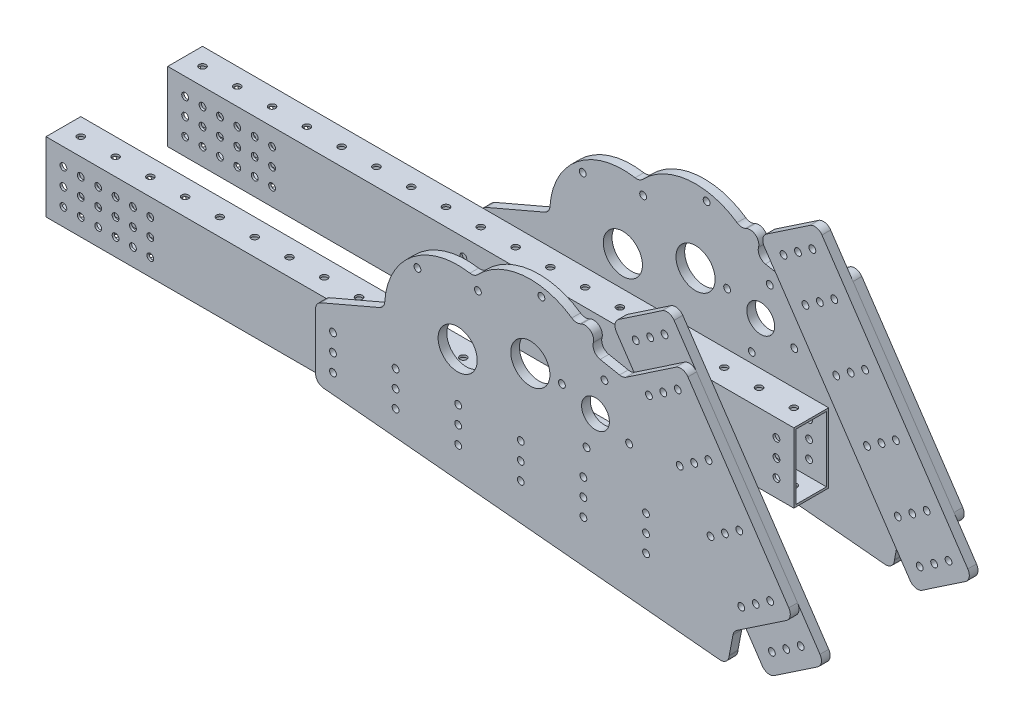
SolidWorks part; units mm, degrees
other "Markup1"
sketch "Sketch2"
sketch "Sketch9" plane through (0, 0, 0) normal (0, 0, 1) x (1, 0, 0)
material "6061-T6 (SS)"
ref_plane "Front Plane" through (0, 0, 0) normal (0, 0, 1) x (1, 0, 0)
ref_plane "Top Plane" through (0, 0, 0) normal (0, 1, 0) x (1, 0, 0)
ref_plane "Right Plane" through (0, 0, 0) normal (1, 0, 0) x (0, 0, -1)
sketch "Grid" plane through (0, 0, 0) normal (0, 0, 1) x (1, 0, 0)
  line L0 (-23.2766, 0) -> (153.3593, 0) construction
  line L1 (0, 0) -> (0, 151.4205) construction
  line L6 (-1009.65, 1168.4) -> (-1009.65, 0) construction
  line L15 (-361.95, 520.7) -> (-803.275, 520.7)
  line L16 (-361.95, 520.7) -> (-361.95, 0)
  line L17 (-361.95, 0) -> (-803.275, 0)
  line L18 (-803.275, 520.7) -> (-803.275, 0)
  line L19 (-803.275, 0) -> (-1244.6, 0)
  line L20 (-803.275, 0) -> (-803.275, 825.5)
  line L21 (-803.275, 825.5) -> (-1244.6, 825.5)
  line L22 (-1244.6, 0) -> (-1244.6, 825.5)
  line L23 (-1030.732, 0) -> (-988.568, 0)
  line L24 (-1030.732, 0) -> (-1030.732, 1168.4)
  line L25 (-1030.732, 1168.4) -> (-988.568, 1168.4)
  line L26 (-988.568, 0) -> (-988.568, 1168.4)
  line L27 (-598.932, 0) -> (-556.768, 0)
  line L28 (-598.932, 0) -> (-598.932, 863.6)
  line L29 (-598.932, 863.6) -> (-556.768, 863.6)
  line L30 (-556.768, 0) -> (-556.768, 863.6)
  line L31 (-577.85, 863.6) -> (-577.85, 0) construction
  line L32 (-361.95, 520.7) -> (-361.95, 596.9) construction
  line L33 (-803.275, 825.5) -> (-803.275, 901.7) construction
  line L34 (-370.0766, 0) -> (-263.7141, 304.8)
  line L35 (-263.7141, 304.8) -> (-157.3516, 0)
  line L36 (-157.3516, 0) -> (-370.0766, 0)
  circle A0 centre (-100.3958, 159.9664) radius 120.65
  dimension "D3" = 241.3
  dimension "D2" = 76.2
  dimension "D4" = 304.8
  dimension "D5" = 212.725
  dimension "D7" = 42.164
  dimension "D8" = 520.7
  dimension "D9" = 304.8
  dimension "D10" = 1168.4
  dimension "D11" = 863.6
  dimension "D12" = 361.95
  dimension "D13" = 577.85
  dimension "D14" = 803.275
  dimension "D15" = 1009.65
sketch "ChassisXY" plane through (0, 0, 0) normal (0, 0, 1) x (1, 0, 0)
  line L0 (755.65, 93.726) -> (95.25, 93.726)
  line L1 (755.65, 93.726) -> (755.65, 42.926)
  line L2 (755.65, 42.926) -> (95.25, 42.926)
  line L3 (95.25, 93.726) -> (95.25, 42.926)
  line L15 (736.7108, 119.126) -> (675.4349, 119.126)
  line L16 (787.4, 42.926) -> (768.35, 42.926)
  line L19 (63.5, 169.926) -> (82.55, 169.926)
  line L20 (736.7108, 119.126) -> (694.5957, 90.719) construction
  line L21 (736.7108, 119.126) -> (717.55, 147.533) construction
  line L22 (694.5957, 90.719) -> (675.4349, 119.126) construction
  line L23 (717.55, 147.533) -> (675.4349, 119.126) construction
  line L27 (63.5, 169.926) -> (63.5, 42.926)
  line L31 (88.9, 42.926) -> (88.9, 1979.9925) construction
  line L32 (62.806, 1979.9925) -> (762, 1979.9925) construction
  line L33 (63.5, 42.926) -> (82.55, 42.926)
  line L36 (88.9, 1320.8) -> (762, 1320.8) construction
  line L37 (88.9, 988.6997) -> (131.0151, 1017.1067) construction
  line L45 (63.5, 42.926) -> (31.75, 42.926)
  line L46 (717.55, 147.533) -> (675.4349, 119.126) construction
  line L47 (717.55, 147.533) -> (-518.4596, 1979.9925) construction
  line L48 (675.4349, 119.126) -> (-560.5747, 1951.5855) construction
  line L49 (-518.4596, 1979.9925) -> (-560.5747, 1951.5855) construction
  line L50 (63.5, 42.926) -> (63.5, 169.926)
  line L51 (0, 74.676) -> (0, 138.176)
  line L52 (31.75, 169.926) -> (63.5, 169.926)
  line L54 (425.45, 93.726) -> (425.45, 42.926) construction
  line L55 (762, 42.926) -> (762, 1979.9925) construction
  line L56 (819.15, 169.926) -> (787.4, 169.926)
  line L57 (850.9, 74.676) -> (850.9, 138.176)
  line L58 (787.4, 42.926) -> (787.4, 169.926)
  line L59 (787.4, 42.926) -> (819.15, 42.926)
  line L60 (82.55, 169.926) -> (82.55, 42.926)
  line L61 (768.35, 169.926) -> (768.35, 42.926)
  line L62 (787.4, 169.926) -> (768.35, 169.926)
  line L63 (787.4, 169.926) -> (787.4, 42.926)
  line L64 (0, 0) -> (0, 200151.4205) construction
  line L65 (-200023.2766, 0) -> (200153.3593, 0) construction
  line L66 (95.25, 152.4) -> (755.65, 152.4) construction
  arc A5 (31.75, 169.926) -> (0, 138.176) centre (31.75, 138.176) ccw
  arc A6 (0, 74.676) -> (31.75, 42.926) centre (31.75, 74.676) ccw
  circle A7 centre (31.75, 74.676) radius 31.75 construction
  circle A8 centre (31.75, 138.176) radius 31.75 construction
  circle A9 centre (819.15, 138.176) radius 31.75 construction
  circle A10 centre (819.15, 74.676) radius 31.75 construction
  arc A11 (850.9, 74.676) -> (819.15, 42.926) centre (819.15, 74.676) cw
  arc A12 (819.15, 169.926) -> (850.9, 138.176) centre (819.15, 138.176) cw
  dimension "D3" = 63.5
  dimension "D1" = 50.8
  dimension "D2" = 56
  dimension "D4" = 38.1
  dimension "D5" = 50.8
  dimension "D6" = 12.7
  dimension "D7" = 19.05
  dimension "D8" = 42.926
  dimension "D9" = 109.474
  dimension "D10" = 25.4
  dimension "D12" = 660.4
  dimension "D13" = 6.35
ref_plane "Plane1" through (561.5696, 378.7835, 0) normal (0.829, 0.5592, 0) x (-0.5592, 0.829, 0)
sketch "carriage geo" plane through (0, 0, 0) normal (0, 0, 1) x (1, 0, 0)
  line L1 (116.0373, 195.326) -> (624.0373, 195.326)
  line L2 (116.0373, 195.326) -> (116.0373, 246.126)
  line L3 (116.0373, 246.126) -> (624.0373, 246.126)
  line L4 (624.0373, 195.326) -> (624.0373, 246.126)
  line L6 (624.0373, 195.326) -> (700.6322, 195.326) construction
  line L17 (717.55, 147.533) -> (-518.4596, 1979.9925) construction
  line L24 (624.0373, 246.126) -> (666.3671, 246.126) construction
  line L33 (666.3671, 246.126) -> (700.6322, 195.326) construction
  line L35 (675.4349, 119.126) -> (-560.5747, 1951.5855) construction
  line L64 (755.65, 93.726) -> (95.25, 93.726) construction
  circle A0 centre (154.1373, 220.726) radius 14.2875
  circle A58 centre (256.8816, 507.741) radius 25.4
  point P4 (353.8882, 537.9448)
  line B0 (120.4355, 364.2548) -> (144.4436, 355.656) construction
  line B1 (345.3934, 565.2279) -> (248.3868, 535.0242)
  line B2 (339.9907, 375.4447) -> (343.9447, 374.0285) construction
  line B3 (348.2442, 386.0326) -> (300.3235, 403.196) construction
  line B4 (308.577, 413.7839) -> (348.5895, 399.4529)
  line B5 (107.1432, 327.1426) -> (206.8255, 291.4401)
  line B6 (112.3162, 360.4178) -> (103.3062, 335.2619)
  line B7 (352.5436, 398.0367) -> (348.5895, 399.4529) construction
  line B8 (366.599, 439.1494) -> (341.413, 442.4393) construction
  line B9 (353.8882, 537.9448) -> (341.413, 442.4393) construction
  line B10 (343.9447, 374.0285) -> (352.5436, 398.0367)
  line B11 (348.5895, 399.4529) -> (308.577, 413.7839)
  line B12 (304.6229, 415.2001) -> (296.0241, 391.1919)
  line B13 (299.9781, 389.7757) -> (339.9907, 375.4447)
  line B14 (140.4752, 344.576) -> (141.8914, 348.5301) construction
  line B15 (129.3385, 325.9381) -> (133.2925, 324.5219) construction
  line B16 (110.7006, 337.0748) -> (109.2844, 333.1207) construction
  line B17 (121.8372, 355.7127) -> (117.8832, 357.1289) construction
  line B18 (117.8832, 357.1289) -> (110.7006, 337.0748)
  line B19 (109.2844, 333.1207) -> (129.3385, 325.9381)
  line B20 (141.8914, 348.5301) -> (121.8372, 355.7127)
  line B21 (133.2925, 324.5219) -> (140.4752, 344.576)
  line B22 (296.0241, 391.1919) -> (299.9781, 389.7757) construction
  line B23 (308.577, 413.7839) -> (304.6229, 415.2001) construction
  arc B24 (248.3868, 535.0242) -> (233.4586, 491.3735) centre (256.8816, 507.741) ccw
  circle B25 centre (256.8816, 507.741) radius 3.1877
  circle B26 centre (353.8882, 537.9448) radius 3.1877
  arc B27 (107.1432, 327.1426) -> (103.3062, 335.2619) centre (109.2844, 333.1207) cw
  circle B28 centre (341.413, 442.4393) radius 30 construction
  arc B29 (121.2422, 363.9009) -> (112.3162, 360.4178) centre (118.2943, 358.2767) ccw
  arc B30 (233.4586, 491.3735) -> (121.2422, 363.9009) centre (161.817, 441.3116) cw
  circle B31 centre (341.413, 442.4393) radius 25.4 construction
  circle B32 centre (366.599, 439.1494) radius 2.4892
  circle B33 centre (338.1231, 417.2533) radius 2.4892
  circle B34 centre (316.2269, 445.7292) radius 2.4892
  circle B35 centre (344.7029, 467.6254) radius 2.4892
  circle B36 centre (341.413, 442.4393) radius 10.16
  circle B37 centre (147.3899, 326.2177) radius 2.4892
  arc B38 (376.4624, 520.4251) -> (367.6342, 457.9958) centre (426.6271, 481.4924) ccw
  arc B39 (367.6342, 457.9958) -> (206.8255, 291.4401) centre (249.6484, 411.0026) cw
  arc B40 (133.2925, 324.5219) -> (129.3385, 325.9381) centre (131.3155, 325.23) cw
  arc B41 (343.9447, 374.0285) -> (339.9907, 375.4447) centre (341.9677, 374.7366) cw
  arc B42 (296.0241, 391.1919) -> (299.9781, 389.7757) centre (298.0011, 390.4838) ccw
  arc B43 (352.5436, 398.0367) -> (348.5895, 399.4529) centre (350.5666, 398.7448) ccw
  arc B44 (304.6229, 415.2001) -> (308.577, 413.7839) centre (306.5999, 414.492) cw
  arc B45 (109.2844, 333.1207) -> (110.7006, 337.0748) centre (109.9925, 335.0977) cw
  arc B46 (117.8832, 357.1289) -> (121.8372, 355.7127) centre (119.8602, 356.4208) cw
  arc B47 (141.8914, 348.5301) -> (140.4752, 344.576) centre (141.1833, 346.553) cw
  circle B48 centre (353.8882, 537.9448) radius 28.575
  line B49 (343.9447, 374.0285) -> (296.1197, 391.1577)
  line B50 (343.9447, 374.0285) -> (318.251, 302.291)
  line B51 (296.1197, 391.1577) -> (270.426, 319.4201)
  line B52 (318.251, 302.291) -> (270.426, 319.4201) construction
  line B53 (141.8571, 348.4344) -> (133.2925, 324.5219) construction
  line B54 (165.7696, 339.8698) -> (237.5071, 314.1761)
  line B55 (157.205, 315.9573) -> (228.9426, 290.2636)
  line B56 (237.5071, 314.1761) -> (228.9426, 290.2636) construction
  line B57 (161.4873, 327.9136) -> (233.2249, 302.2198) construction
  line B58 (165.7696, 339.8698) -> (157.205, 315.9573)
  line B59 (133.2925, 324.5219) -> (157.205, 315.9573) construction
  line B60 (141.8571, 348.4344) -> (165.7696, 339.8698) construction
  line B61 (308.4359, 312.5514) -> (331.9885, 378.3108) construction
  line B62 (320.0322, 382.5931) -> (294.3385, 310.8556) construction
  arc B63 (155.075, 274.6929) -> (165.7608, 168.0174) centre (154.1373, 220.726) ccw
  circle B64 centre (176.5553, 212.6967) radius 2.4892
  circle B65 centre (158.3928, 197.2968) radius 2.4892
  circle B66 centre (135.9748, 205.3261) radius 2.4892
  circle B67 centre (131.7194, 228.7553) radius 2.4892
  circle B68 centre (149.8819, 244.1552) radius 2.4892
  circle B69 centre (172.2999, 236.1259) radius 2.4892
  circle B70 centre (154.1373, 220.726) radius 23.8125 construction
  circle B71 centre (308.4359, 312.5514) radius 2.4892
  arc B72 (165.7608, 168.0174) -> (155.075, 274.6929) centre (154.1373, 220.726) ccw construction
  circle B73 centre (227.2467, 304.361) radius 2.4892
  circle B74 centre (284.5234, 321.116) radius 2.4892
  arc B75 (290.7123, 376.06) -> (193.2811, 330.0162) centre (218.9748, 401.7538) cw
  arc B76 (318.251, 302.291) -> (165.7608, 168.0174) centre (120.5341, 373.1059) cw
  circle B77 centre (312.7182, 324.5077) radius 2.4892
  circle B78 centre (288.8057, 333.0722) radius 2.4892
  circle B79 centre (317.0005, 336.4639) radius 2.4892
  circle B80 centre (293.088, 345.0285) radius 2.4892
  circle B81 centre (321.2828, 348.4202) radius 2.4892
  circle B82 centre (297.3703, 356.9847) radius 2.4892
  circle B83 centre (325.5651, 360.3764) radius 2.4892
  circle B84 centre (301.6526, 368.941) radius 2.4892
  circle B85 centre (329.8473, 372.3327) radius 2.4892
  circle B86 centre (305.9348, 380.8972) radius 2.4892
  arc B87 (162.2796, 314.1398) -> (155.075, 274.6929) centre (155.4279, 295.0098) cw
  circle B88 centre (215.2905, 308.6433) radius 2.4892
  circle B89 centre (203.3342, 312.9256) radius 2.4892
  circle B90 centre (191.378, 317.2079) radius 2.4892
  circle B91 centre (179.4217, 321.4901) radius 2.4892
  circle B92 centre (167.4655, 325.7724) radius 2.4892
  dimension "D2" = 28.575
  dimension "D3" = 25.4
  dimension "D4" = 38.1
  dimension "D8" = 101.6
  dimension "D5" = 50.8
  dimension "D1" = 50.8
  dimension "D6" = 12.7
  dimension "D7" = 508
sketch_block_instance "Block25-1"
sketch_block "Block25"
sketch_block_instance "Block26-1"
sketch_block "Block26"
sketch "carrriageyz" plane through (561.5696, 378.7835, 0) normal (0.829, 0.5592, 0) x (-0.5592, 0.829, 0)
  line L0 (-313.2035, 69.85) -> (769.957, 69.85) construction
  line L1 (769.957, -69.85) -> (-313.2035, -69.85) construction
  line L2 (-262.4035, 69.85) -> (-262.4035, -69.85) construction
  line L4 (-313.2035, 69.85) -> (-313.2035, -69.85) construction
  line L5 (-313.2035, 0) -> (-278.9385, 0) construction
  line L6 (769.957, 69.85) -> (769.957, -69.85) construction
  line L7 (-249.7114, 57.15) -> (-249.7114, 50.8)
  line L8 (-249.7114, 57.15) -> (-97.3114, 57.15)
  line L9 (-249.7114, 50.8) -> (-97.3114, 50.8)
  line L10 (-97.3114, 57.15) -> (-97.3114, 50.8)
  line L11 (1088.9959, 0) -> (-1088.9959, 0) construction
  line L12 (-97.3114, -57.15) -> (-97.3114, -50.8)
  line L13 (-249.7114, -50.8) -> (-97.3114, -50.8)
  line L14 (-249.7114, -57.15) -> (-97.3114, -57.15)
  line L15 (-249.7114, -57.15) -> (-249.7114, -50.8)
  line L16 (-218.5469, 31.75) -> (-148.6639, 31.75)
  line L17 (-174.4547, 57.15) -> (-206.8488, 57.15)
  line L19 (-221.2897, -57.15) -> (-160.0138, -57.15)
  line L21 (-219.5489, -57.15) -> (-127.4739, -57.15)
  line L22 (-219.5489, 63.5) -> (-127.4739, 63.5)
  line L23 (-219.5489, 63.5) -> (-219.5489, 57.15)
  line L24 (-219.5489, 57.15) -> (-127.4739, 57.15)
  line L25 (-127.4739, 63.5) -> (-127.4739, 57.15)
  line L26 (-127.4739, -63.5) -> (-127.4739, -57.15)
  line L27 (-219.5489, -63.5) -> (-127.4739, -63.5)
  line L28 (-219.5489, -63.5) -> (-219.5489, -57.15)
  line L29 (-218.5469, 31.75) -> (-218.5469, -31.75)
  line L30 (-218.5469, -31.75) -> (-148.6639, -31.75)
  line L31 (-148.6639, 31.75) -> (-148.6639, -31.75)
  line L33 (-97.3114, -69.1134) -> (-125.8864, -69.1134)
  line L34 (-97.3114, 57.15) -> (-125.8864, 57.15)
  line L35 (-97.3114, 57.15) -> (-97.3114, 69.1134)
  line L36 (-97.3114, 69.1134) -> (-125.8864, 69.1134)
  line L37 (-125.8864, 57.15) -> (-125.8864, 69.1134)
  line L38 (-249.7114, 57.15) -> (-221.1364, 57.15)
  line L39 (-249.7114, 57.15) -> (-249.7114, 69.1134)
  line L40 (-249.7114, 69.1134) -> (-221.1364, 69.1134)
  line L41 (-221.1364, 57.15) -> (-221.1364, 69.1134)
  line L42 (-125.8864, -57.15) -> (-125.8864, -69.1134)
  line L43 (-97.3114, -57.15) -> (-125.8864, -57.15)
  line L44 (-97.3114, -57.15) -> (-97.3114, -69.1134)
  line L45 (-249.7114, -69.1134) -> (-221.1364, -69.1134)
  line L46 (-221.1364, -57.15) -> (-221.1364, -69.1134)
  line L47 (-249.7114, -57.15) -> (-221.1364, -57.15)
  line L48 (-249.7114, -57.15) -> (-249.7114, -69.1134)
  line L49 (-111.5989, 69.1134) -> (-111.5989, -69.1134) construction
  line L50 (-235.4239, 69.1134) -> (-235.4239, -69.1134) construction
  point P4 (-313.2035, 0)
  point P31 (-148.6639, 0)
  point P41 (-190.6518, 57.15)
  point P53 (-111.5989, 0)
  dimension "D1" = 139.7
  dimension "D2" = 12.7
  dimension "D3" = 6.35
  dimension "D4" = 63.5
  dimension "D5" = 6.35
  dimension "D6" = 152.4
  dimension "D7" = 28.575
  dimension "D8" = 11.9634
  dimension "D9" = 50.8
  dimension "D10" = 1.5875
  dimension "D11" = 1.5875
ref_plane "bearing block interface plane" through (0, 0, 57.15) normal (0, 0, 1) x (1, 0, 0)
sketch "bearing block interface plate" plane through (0, 0, 57.15) normal (0, 0, 1) x (1, 0, 0)
  line L0 (529.0514, 336.1484) -> (571.1665, 364.5554)
  line L1 (529.0514, 336.1484) -> (642.6794, 167.688)
  line L2 (571.1665, 364.5554) -> (684.7945, 196.095)
  line L3 (642.6794, 167.688) -> (684.7945, 196.095)
  line L4 (675.4349, 119.126) -> (-560.5747, 1951.5855) construction
  line L5 (717.55, 147.533) -> (-518.4596, 1979.9925) construction
  line L6 (635.5777, 178.2167) -> (677.6928, 206.6237) construction
  line L7 (585.8654, 251.9182) -> (627.9805, 280.3252) construction
  line L8 (626.7005, 191.3777) -> (668.8156, 219.7847) construction
  line L10 (545.0304, 312.4586) -> (587.1455, 340.8656) construction
  line L12 (528.3092, 320.3288) -> (546.682, 332.7214) construction
  line L15 (606.2073, 289.894) -> (628.6962, 256.5529) construction
  line L16 (522.4272, 322.7212) -> (526.7202, 333.2764) construction
  line L17 (529.0514, 336.1484) -> (536.1532, 325.6196) construction
  line L18 (527.0768, 314.0996) -> (540.247, 311.4938) construction
  line L19 (627.7485, 166.576) -> (639.1433, 166.6024) construction
  line L20 (621.4964, 174.1167) -> (624.014, 187.3041) construction
  circle A0 centre (646.1065, 185.3185) radius 2.4892
  circle A1 centre (656.6352, 192.4202) radius 2.4892
  circle A2 centre (667.164, 199.522) radius 2.4892
  circle A3 centre (567.7395, 346.9249) radius 2.4892
  circle A4 centre (557.2107, 339.8231) radius 2.4892
  circle A5 centre (546.682, 332.7214) radius 2.4892
  arc A7 (522.4272, 322.7212) -> (527.0768, 314.0996) centre (528.3092, 320.3288) ccw construction
  circle A12 centre (562.6609, 309.0316) radius 2.4892
  circle A13 centre (573.1897, 316.1334) radius 2.4892
  circle A14 centre (583.7185, 323.2351) radius 2.4892
  circle A15 centre (606.2073, 289.894) radius 2.4892
  circle A16 centre (595.6786, 282.7922) radius 2.4892
  circle A17 centre (585.1498, 275.6905) radius 2.4892
  circle A18 centre (628.6962, 256.5529) radius 2.4892
  circle A19 centre (618.1674, 249.4511) radius 2.4892
  circle A20 centre (607.6387, 242.3494) radius 2.4892
  circle A21 centre (651.1851, 223.2117) radius 2.4892
  circle A22 centre (640.6563, 216.11) radius 2.4892
  circle A23 centre (630.1275, 209.0082) radius 2.4892
  arc A24 (526.7202, 333.2764) -> (529.0514, 336.1484) centre (532.6023, 330.884) cw construction
  arc A25 (540.247, 311.4938) -> (545.0304, 312.4586) centre (541.4795, 317.723) ccw construction
  arc A26 (639.1433, 166.6024) -> (642.6794, 167.688) centre (639.1286, 172.9523) ccw construction
  arc A27 (627.7485, 166.576) -> (621.4964, 174.1167) centre (627.7337, 172.9259) cw construction
  arc A28 (624.014, 187.3041) -> (626.7005, 191.3777) centre (630.2514, 186.1133) cw construction
  point P28 (617.4518, 273.2234)
  point P64 (0, 0)
  point P70 (671.8417, 223.2117)
  point P71 (668.8156, 219.7847)
  dimension "D3" = 4.9784
  dimension "D8" = 12.7
  dimension "D10" = 2
  dimension "D13" = 6.35
  dimension "D1" = 12.7
  dimension "D2" = 12.7
  dimension "D4" = 12.7
  dimension "D5" = 28.575
  dimension "D6" = 203.2
  dimension "D7" = 4.7625
  dimension "D9" = 9.4615
  dimension "D11" = 4
  dimension "D12" = 12.7
extrude "Boss-Extrude1" add sketch "bearing block interface plate" against normal blind 6.35
fillet "Fillet2" radius 6.35 4 edges at (642.6794, 167.688, 53.975) (571.1665, 364.5554, 53.975) (529.0514, 336.1484, 53.975) (684.7945, 196.095, 53.975)
ref_plane "carriage support plane" through (0, 0, 63.5) normal (0, 0, 1) x (1, 0, 0)
sketch "plate+gb" plane through (0, 0, 63.5) normal (0, 0, 1) x (1, 0, 0)
  line L1 (717.55, 147.533) -> (-518.4596, 1979.9925) construction
  line L3 (116.0373, 195.326) -> (624.0373, 195.326) construction
  line L4 (319.2373, 195.326) -> (627.1295, 166.4772)
  line L7 (668.3717, 220.4428) -> (587.5893, 340.2076)
  line L8 (509.1308, 327.7242) -> (407.5328, 284.067) construction
  line L9 (528.9804, 336.2537) -> (509.1308, 327.7242)
  line L10 (116.0373, 246.126) -> (624.0373, 246.126) construction
  line L11 (319.2373, 246.126) -> (319.2373, 195.326)
  line L12 (624.0373, 195.326) -> (624.0373, 246.126) construction
  line L13 (587.5893, 340.2076) -> (545.9795, 312.1414)
  line L16 (626.7619, 192.3766) -> (668.3717, 220.4428)
  line L17 (626.7005, 191.3777) -> (668.8156, 219.7847) construction
  line L18 (545.0304, 312.4586) -> (587.1455, 340.8656) construction
  line L19 (423.0019, 268.351) -> (154.1373, 220.726) construction
  line L20 (422.4031, 284.6145) -> (152.1515, 274.6645) construction
  line L21 (428.0259, 252.8714) -> (170.7996, 169.3872) construction
  line L22 (523.6581, 277.876) -> (530.2321, 302.4105) construction
  line L24 (369.6648, 267.7949) -> (319.2373, 246.126)
  line L26 (407.5328, 284.067) -> (369.6648, 267.7949) construction
  line L27 (435.2885, 320.2566) -> (440.2811, 305.1347) construction
  line L28 (623.8893, 187.3279) -> (621.3716, 174.1405)
  line L29 (627.7488, 166.449) -> (639.1436, 166.4754)
  line L30 (526.6026, 333.3242) -> (522.3095, 322.7691)
  line L31 (527.0521, 313.975) -> (540.2224, 311.3692)
  line L32 (526.6026, 333.3242) -> (522.3095, 322.7691)
  line L33 (527.0521, 313.975) -> (541.1961, 311.1765)
  line L34 (624.0754, 188.303) -> (621.3716, 174.1405)
  line L36 (389.6951, 310.0141) -> (397.6253, 300.0943) construction
  line L37 (485.2505, 338.4129) -> (483.0634, 325.9027) construction
  circle A0 centre (476.0648, 285.8698) radius 14.2875
  circle A1 centre (423.0019, 268.351) radius 14.2875
  arc A2 (155.075, 274.6929) -> (165.7608, 168.0174) centre (154.1373, 220.726) ccw construction
  arc A4 (165.7608, 168.0174) -> (155.075, 274.6929) centre (154.1373, 220.726) ccw construction
  circle A5 centre (523.6581, 277.876) radius 10.16
  circle A12 centre (523.6581, 277.876) radius 25.4 construction
  circle A13 centre (523.6581, 277.876) radius 7.62 construction
  circle A14 centre (476.0648, 285.8698) radius 40.64 construction
  circle A15 centre (476.0648, 285.8698) radius 15.24 construction
  circle A16 centre (423.0019, 268.351) radius 40.64 construction
  circle A17 centre (423.0019, 268.351) radius 16.2745 construction
  circle A18 centre (530.2321, 302.4105) radius 2.4892
  circle A19 centre (548.1926, 271.302) radius 2.4892
  circle A20 centre (517.0841, 253.3415) radius 2.4892
  circle A21 centre (499.1236, 284.45) radius 2.4892
  circle A22 centre (651.1851, 223.2117) radius 2.4892 construction
  circle A23 centre (640.6563, 216.11) radius 2.4892 construction
  circle A24 centre (630.1275, 209.0082) radius 2.4892 construction
  circle A25 centre (607.6387, 242.3494) radius 2.4892 construction
  circle A26 centre (618.1674, 249.4511) radius 2.4892 construction
  circle A27 centre (628.6962, 256.5529) radius 2.4892 construction
  circle A28 centre (606.2073, 289.894) radius 2.4892 construction
  circle A29 centre (595.6786, 282.7922) radius 2.4892 construction
  circle A30 centre (585.1498, 275.6905) radius 2.4892 construction
  circle A31 centre (562.6609, 309.0316) radius 2.4892 construction
  circle A32 centre (573.1897, 316.1334) radius 2.4892 construction
  circle A33 centre (583.7185, 323.2351) radius 2.4892 construction
  circle A34 centre (651.1851, 223.2117) radius 2.4892
  circle A35 centre (523.6581, 277.876) radius 30 construction
  circle A37 centre (640.6563, 216.11) radius 2.4892
  circle A40 centre (630.1275, 209.0082) radius 2.4892
  circle A41 centre (607.6387, 242.3494) radius 2.4892
  circle A42 centre (618.1674, 249.4511) radius 2.4892
  circle A43 centre (628.6962, 256.5529) radius 2.4892
  circle A44 centre (606.2073, 289.894) radius 2.4892
  circle A45 centre (595.6786, 282.7922) radius 2.4892
  circle A46 centre (585.1498, 275.6905) radius 2.4892
  circle A47 centre (562.6609, 309.0316) radius 2.4892
  circle A48 centre (573.1897, 316.1334) radius 2.4892
  circle A49 centre (583.7185, 323.2351) radius 2.4892
  circle A53 centre (528.3092, 320.3288) radius 9.525 construction
  arc A56 (435.2885, 320.2566) -> (369.6648, 267.7949) centre (423.0019, 268.351) ccw
  arc A57 (541.1961, 311.1765) -> (545.9795, 312.1414) centre (542.4286, 317.4058) ccw
  arc A58 (624.0754, 188.303) -> (626.7619, 192.3766) centre (630.3128, 187.1122) cw
  arc A59 (513.4373, 329.5747) -> (522.0656, 322.0516) centre (515.9443, 323.7406) cw
  arc A60 (626.6295, 191.483) -> (623.8893, 187.3279) centre (630.2514, 186.1133) ccw
  arc A61 (528.9804, 336.2537) -> (526.6026, 333.3242) centre (532.6023, 330.884) ccw
  arc A62 (522.3095, 322.7691) -> (527.0521, 313.975) centre (528.3092, 320.3288) ccw
  arc A63 (540.2224, 311.3692) -> (545.1014, 312.3534) centre (541.4795, 317.723) ccw
  arc A64 (528.9804, 336.2537) -> (526.6026, 333.3242) centre (532.6023, 330.884) ccw
  arc A65 (522.3095, 322.7691) -> (527.0521, 313.975) centre (528.3092, 320.3288) ccw
  arc A66 (621.3716, 174.1405) -> (627.7488, 166.449) centre (627.7337, 172.9259) ccw
  arc A67 (639.1436, 166.4754) -> (642.7505, 167.5827) centre (639.1286, 172.9523) ccw
  arc A68 (626.6295, 191.483) -> (623.8893, 187.3279) centre (630.2514, 186.1133) ccw
  arc A69 (621.3716, 174.1405) -> (627.1295, 166.4772) centre (627.7337, 172.9259) ccw
  arc A70 (435.2885, 320.2566) -> (509.1308, 327.7242) centre (476.0648, 285.8698) cw
  circle A71 centre (437.7848, 312.6957) radius 2.4892
  circle A72 centre (484.157, 332.1578) radius 2.4892
  circle A73 centre (393.6602, 305.0542) radius 2.4892
  point P64 (523.6581, 277.876)
  dimension "D2" = 50.8
  dimension "D15" = 28.575
  dimension "D16" = 20.32
  dimension "D18" = 4.9784
  dimension "D14" = 6.35
  dimension "D23" = 19.05
  dimension "D25" = 4.9784
  dimension "D1" = 304.8
  dimension "D11" = 0.7937
  dimension "D12" = 0.7937
  dimension "D19" = 15
  dimension "D8" = 273.05
  dimension "D10" = 22.225
  dimension "D9" = 25.4
  dimension "D20" = 31.75
  dimension "D24" = 12.7
  dimension "D26" = 50.8
  dimension "D13" = 0.127
  dimension "D21" = 0.127
  dimension "D17" = 4
extrude "Boss-Extrude2" add sketch "plate+gb" against normal blind 6.35 separate body contours A69 L34 A58 L16 L7 L13 A57 L33 A65 L32 A64 L9 L11 L4 A49 A48 A47 A46 A45 A44 A43 A42 A41 A40 A37 A34 A21 A20 A19 A18 A5 A1 region at (496.5673, 246.5069, 63.5)
fillet "Fillet1" radius 6.35 8 edges at (668.3717, 220.4428, 60.325) (587.5893, 340.2076, 60.325) (319.2373, 195.326, 60.325) (627.1295, 166.4772, 60.325) (435.2885, 320.2566, 60.325) (369.6648, 267.7949, 60.325) (509.1308, 327.7242, 60.325) (319.2373, 246.126, 60.325)
ref_plane "tubeplate" through (0, 0, 57.15) normal (0, 0, 1) x (1, 0, 0)
sketch "tube" plane through (0, 0, 57.15) normal (0, 0, 1) x (1, 0, 0)
  line L0 (116.0373, 246.126) -> (624.0373, 246.126) construction
  line L1 (573.2373, 246.126) -> (116.0373, 246.126)
  line L2 (573.2373, 246.126) -> (573.2373, 195.326)
  line L3 (573.2373, 195.326) -> (116.0373, 195.326)
  line L4 (116.0373, 246.126) -> (116.0373, 195.326)
  line L6 (624.0373, 195.326) -> (624.0373, 246.126) construction
  line L7 (560.5373, 246.126) -> (560.5373, 195.326) construction
  line L8 (319.2373, 246.126) -> (319.2373, 195.326) construction
  line L9 (128.7373, 246.126) -> (128.7373, 195.326) construction
  line L10 (116.0373, 195.326) -> (624.0373, 195.326) construction
  circle A0 centre (560.5373, 220.726) radius 2.4892
  circle A1 centre (560.5373, 208.026) radius 2.4892
  circle A2 centre (560.5373, 233.426) radius 2.4892
  circle A3 centre (514.8173, 208.026) radius 2.4892
  circle A4 centre (514.8173, 220.726) radius 2.4892
  circle A5 centre (514.8173, 233.426) radius 2.4892
  circle A6 centre (469.0973, 208.026) radius 2.4892
  circle A7 centre (469.0973, 220.726) radius 2.4892
  circle A8 centre (469.0973, 233.426) radius 2.4892
  circle A9 centre (423.3773, 208.026) radius 2.4892
  circle A10 centre (423.3773, 220.726) radius 2.4892
  circle A11 centre (423.3773, 233.426) radius 2.4892
  circle A12 centre (377.6573, 208.026) radius 2.4892
  circle A13 centre (377.6573, 220.726) radius 2.4892
  circle A14 centre (377.6573, 233.426) radius 2.4892
  circle A15 centre (331.9373, 208.026) radius 2.4892
  circle A16 centre (331.9373, 220.726) radius 2.4892
  circle A17 centre (331.9373, 233.426) radius 2.4892
  circle A18 centre (128.7373, 220.726) radius 2.4892
  circle A19 centre (128.7373, 208.026) radius 2.4892
  circle A20 centre (128.7373, 233.426) radius 2.4892
  circle A21 centre (141.4373, 220.726) radius 2.4892
  circle A22 centre (141.4373, 208.026) radius 2.4892
  circle A23 centre (141.4373, 233.426) radius 2.4892
  circle A24 centre (154.1373, 220.726) radius 2.4892
  circle A25 centre (154.1373, 208.026) radius 2.4892
  circle A26 centre (154.1373, 233.426) radius 2.4892
  circle A27 centre (166.8373, 220.726) radius 2.4892
  circle A28 centre (166.8373, 208.026) radius 2.4892
  circle A29 centre (166.8373, 233.426) radius 2.4892
  circle A30 centre (179.5373, 220.726) radius 2.4892
  circle A31 centre (179.5373, 208.026) radius 2.4892
  circle A32 centre (179.5373, 233.426) radius 2.4892
  circle A33 centre (192.2373, 220.726) radius 2.4892
  circle A34 centre (192.2373, 208.026) radius 2.4892
  circle A35 centre (192.2373, 233.426) radius 2.4892
  point P89 (0, 0)
  point P90 (0, 0)
  point P91 (0, 0)
  point P92 (0, 0)
  point P93 (0, 0)
  point P94 (0, 0)
  point P95 (0, 0)
  point P96 (0, 0)
  dimension "D3" = 4.9784
  dimension "D8" = 4.9784
  dimension "D1" = 50.8
  dimension "D2" = 12.7
  dimension "D4" = 12.7
  dimension "D5" = 12.7
  dimension "D7" = 12.7
  dimension "D9" = 12.7
  dimension "D10" = 12.7
  dimension "D11" = 12.7
  dimension "D13" = 12.7
  dimension "D6" = 6
  dimension "D12" = 6
extrude "Boss-Extrude3" add sketch "tube" against normal blind 25.4 separate body contours L1 L4 L3 L2 A35 A34 A33 A32 A31 A30 A29 A28 A27 A26 A25 A24 A23 A22 A21 A20 A19 A18 A17 A16 A15 A14 A13 | A2 | A0 | A1 | A3 | A4 | A5 | A8 | A7 | A9 | A6 | A10 | A17 | A14 | A13 | A12 | A15 | A16 | A11 | A35 | A32 | A29 | A26 | A23 | A20 | A18 | A21 | A24 | A27 | A30 | A33 | A34 | A31 | A28 | A25 | A22 | A19 region at (345.9214, 220.726, 57.15) region at (560.5373, 220.726, 57.15) region at (560.5373, 208.026, 57.15) region at (560.5373, 233.426, 57.15) region at (514.8173, 208.026, 57.15) region at (514.8173, 220.726, 57.15) region at (514.8173, 233.426, 57.15) region at (469.0973, 208.026, 57.15) region at (469.0973, 220.726, 57.15) region at (469.0973, 233.426, 57.15) region at (423.3773, 208.026, 57.15) region at (423.3773, 220.726, 57.15) region at (423.3773, 233.426, 57.15) region at (377.6573, 208.026, 57.15) region at (377.6573, 220.726, 57.15) region at (377.6573, 233.426, 57.15) region at (331.9373, 208.026, 57.15) region at (331.9373, 220.726, 57.15) region at (331.9373, 233.426, 57.15) region at (128.7373, 220.726, 57.15) region at (128.7373, 208.026, 57.15) region at (128.7373, 233.426, 57.15) region at (141.4373, 220.726, 57.15) region at (141.4373, 208.026, 57.15) region at (141.4373, 233.426, 57.15) region at (154.1373, 220.726, 57.15) region at (154.1373, 208.026, 57.15) region at (154.1373, 233.426, 57.15) region at (166.8373, 220.726, 57.15) region at (166.8373, 208.026, 57.15) region at (166.8373, 233.426, 57.15) region at (179.5373, 220.726, 57.15) region at (179.5373, 208.026, 57.15) region at (179.5373, 233.426, 57.15) region at (192.2373, 220.726, 57.15) region at (192.2373, 208.026, 57.15) region at (192.2373, 233.426, 57.15)
shell "Shell2" thickness 1.5875 removed face at (573.2373, 220.726, 44.45) removed face at (116.0373, 220.726, 44.45)
sketch "Sketch11" plane through (0, 246.126, 0) normal (0, 1, 0) x (1, 0, 0)
  line L0 (116.0373, -44.45) -> (573.2373, -44.45) construction
  line L1 (116.0373, -31.75) -> (116.0373, -57.15) construction
  line L2 (573.2373, -31.75) -> (573.2373, -57.15) construction
  circle A0 centre (560.5373, -44.45) radius 2.4892
  circle A1 centre (535.1373, -44.45) radius 2.4892
  circle A2 centre (509.7373, -44.45) radius 2.4892
  circle A3 centre (484.3373, -44.45) radius 2.4892
  circle A4 centre (458.9373, -44.45) radius 2.4892
  circle A5 centre (433.5373, -44.45) radius 2.4892
  circle A6 centre (408.1373, -44.45) radius 2.4892
  circle A7 centre (382.7373, -44.45) radius 2.4892
  circle A8 centre (357.3373, -44.45) radius 2.4892
  circle A9 centre (331.9373, -44.45) radius 2.4892
  circle A10 centre (306.5373, -44.45) radius 2.4892
  circle A11 centre (281.1373, -44.45) radius 2.4892
  circle A12 centre (255.7373, -44.45) radius 2.4892
  circle A13 centre (230.3373, -44.45) radius 2.4892
  circle A14 centre (204.9373, -44.45) radius 2.4892
  circle A15 centre (179.5373, -44.45) radius 2.4892
  circle A16 centre (154.1373, -44.45) radius 2.4892
  circle A17 centre (128.7373, -44.45) radius 2.4892
  dimension "D1" = 4.9784
  dimension "D2" = 12.7
  dimension "D4" = 25.4
  dimension "D3" = 18
extrude "Cut-Extrude4" cut sketch "Sketch11" against normal through all
extrude "Cut-Extrude2" cut sketch "tube<4>" against normal through all contours A2 | A0 | A1 | A3 | A4 | A5 | A8 | A7 | A10 | A11 | A14 | A12 | A17 | A16 | A35 | A34 | A32 | A30 | A29 | A27 | A24 | A22 | A19 | A31 | A6 | A9 | A13 | A15 | A33 | A26 | A23 | A20 | A18 | A21 | A25 | A28 region at (560.5373, 220.726, 57.15) region at (560.5373, 208.026, 57.15) region at (560.5373, 233.426, 57.15) region at (514.8173, 208.026, 57.15) region at (514.8173, 220.726, 57.15) region at (514.8173, 233.426, 57.15) region at (469.0973, 220.726, 57.15) region at (469.0973, 233.426, 57.15) region at (423.3773, 220.726, 57.15) region at (423.3773, 233.426, 57.15) region at (377.6573, 208.026, 57.15) region at (377.6573, 233.426, 57.15) region at (331.9373, 220.726, 57.15) region at (331.9373, 233.426, 57.15) region at (128.7373, 208.026, 57.15) region at (141.4373, 208.026, 57.15) region at (154.1373, 220.726, 57.15) region at (166.8373, 220.726, 57.15) region at (166.8373, 233.426, 57.15) region at (179.5373, 220.726, 57.15) region at (179.5373, 208.026, 57.15) region at (179.5373, 233.426, 57.15) region at (192.2373, 208.026, 57.15) region at (192.2373, 233.426, 57.15)
sketch "tube<4>" plane through (0, 0, 57.15) normal (0, 0, 1) x (1, 0, 0) same geometry as "tube"
sketch "Sketch10" plane through (0, 0, 63.5) normal (0, 0, 1) x (1, 0, 0)
  circle A0 centre (469.0973, 208.026) radius 2.4892 construction
  circle A1 centre (423.3773, 208.026) radius 2.4892 construction
  circle A2 centre (377.6573, 208.026) radius 2.4892 construction
  circle A3 centre (331.9373, 208.026) radius 2.4892 construction
  circle A4 centre (331.9373, 220.726) radius 2.4892 construction
  circle A5 centre (377.6573, 220.726) radius 2.4892 construction
  circle A6 centre (423.3773, 220.726) radius 2.4892 construction
  circle A7 centre (469.0973, 220.726) radius 2.4892 construction
  circle A8 centre (514.8173, 220.726) radius 2.4892 construction
  circle A9 centre (514.8173, 208.026) radius 2.4892 construction
  circle A10 centre (560.5373, 208.026) radius 2.4892 construction
  circle A11 centre (560.5373, 220.726) radius 2.4892 construction
  circle A12 centre (560.5373, 233.426) radius 2.4892 construction
  circle A13 centre (514.8173, 233.426) radius 2.4892 construction
  circle A14 centre (469.0973, 233.426) radius 2.4892 construction
  circle A15 centre (423.3773, 233.426) radius 2.4892 construction
  circle A16 centre (377.6573, 233.426) radius 2.4892 construction
  circle A17 centre (331.9373, 233.426) radius 2.4892 construction
  circle A18 centre (469.0973, 208.026) radius 2.4892
  circle A19 centre (423.3773, 208.026) radius 2.4892
  circle A20 centre (377.6573, 208.026) radius 2.4892
  circle A21 centre (331.9373, 208.026) radius 2.4892
  circle A22 centre (331.9373, 220.726) radius 2.4892
  circle A23 centre (377.6573, 220.726) radius 2.4892
  circle A24 centre (423.3773, 220.726) radius 2.4892
  circle A25 centre (469.0973, 220.726) radius 2.4892
  circle A26 centre (514.8173, 220.726) radius 2.4892
  circle A27 centre (514.8173, 208.026) radius 2.4892
  circle A28 centre (560.5373, 208.026) radius 2.4892
  circle A29 centre (560.5373, 220.726) radius 2.4892
  circle A30 centre (560.5373, 233.426) radius 2.4892
  circle A31 centre (514.8173, 233.426) radius 2.4892
  circle A32 centre (469.0973, 233.426) radius 2.4892
  circle A33 centre (423.3773, 233.426) radius 2.4892
  circle A34 centre (377.6573, 233.426) radius 2.4892
  circle A35 centre (331.9373, 233.426) radius 2.4892
extrude "Cut-Extrude3" cut sketch "Sketch10" against normal through all
mirror "Mirror1" about plane through (0, 0, 0) normal (0, 0, 1) of bodies 105 104 101
equation "\"D3@plate+gb\" = 12 / 20"
equation "\"D4@plate+gb\" = 64 / 20"
equation "\"D5@plate+gb\" = 24 / 20"
equation "\"D6@plate+gb\" = 64 / 20"
equation "\"D7@plate+gb\" = 0.25 /  ( sin ( 180 / 16 )  ) "
equation "\"D22@plate+gb\"=60mm"
